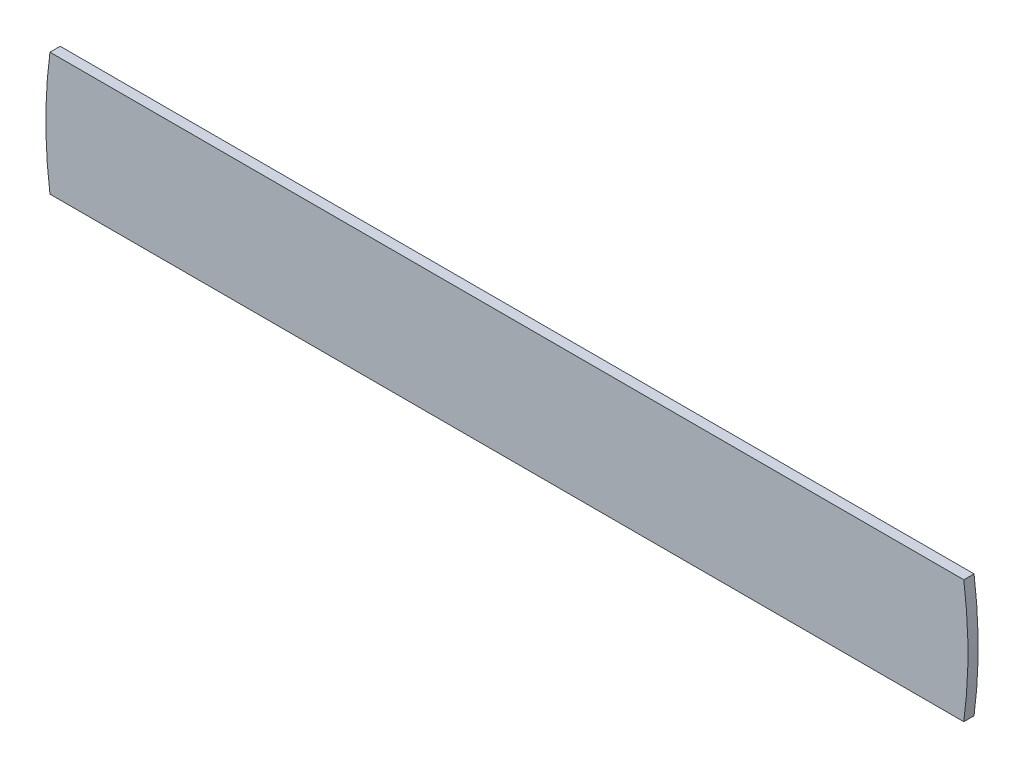
SolidWorks part; units mm, degrees
ref_plane "Plano frontal" through (0, 0, 0) normal (0, 0, 1) x (1, 0, 0)
ref_plane "Plano superior" through (0, 0, 0) normal (0, 1, 0) x (1, 0, 0)
ref_plane "Plano direito" through (0, 0, 0) normal (1, 0, 0) x (0, 0, -1)
sketch "Esboço1" plane through (0, 0, 0) normal (0, 0, 1) x (1, 0, 0)
  line L1 (-89.1964, 12) -> (89.1964, 12)
  line L2 (89.1964, -12) -> (-89.1964, -12)
  arc A1 (89.1964, -12) -> (89.1964, 12) centre (0, 0) ccw
  arc A2 (-89.1964, 12) -> (-89.1964, -12) centre (0, 0) ccw
  point P6 (0, 0)
  point P9 (0, 12)
  point P12 (0, -12)
base flange "Flange-base1" sketch "Esboço1" thickness 2 reverse thickness direction no parameters "D1"=10
sketch "Curva-Linhas1" [suppressed] plane through (0, 0, 0) normal (0, 1, 0) x (1, 0, 0)
sketch "Caixa delimitadora1" [suppressed] plane through (0, 0, 0) normal (0, 1, 0) x (1, 0, 0)
sheet metal parameters "Chapa metálica1" thickness 2 parameters "D1"=10
flat pattern "Padrão-Plano1" [suppressed]
sketch "Curva-Linhas2" plane through (0, 0, 0) normal (0, 1, 0) x (1, 0, 0)
sketch3d "Caixa delimitadora2" [suppressed]
  line L0 (-90, -12, 0) -> (90, -12, 0) construction
  line L1 (-90, 12, 0) -> (90, 12, 0) construction
  line L2 (-90, -12, 0) -> (-90, 12, 0) construction
  line L3 (90, -12, 0) -> (90, 12, 0) construction
